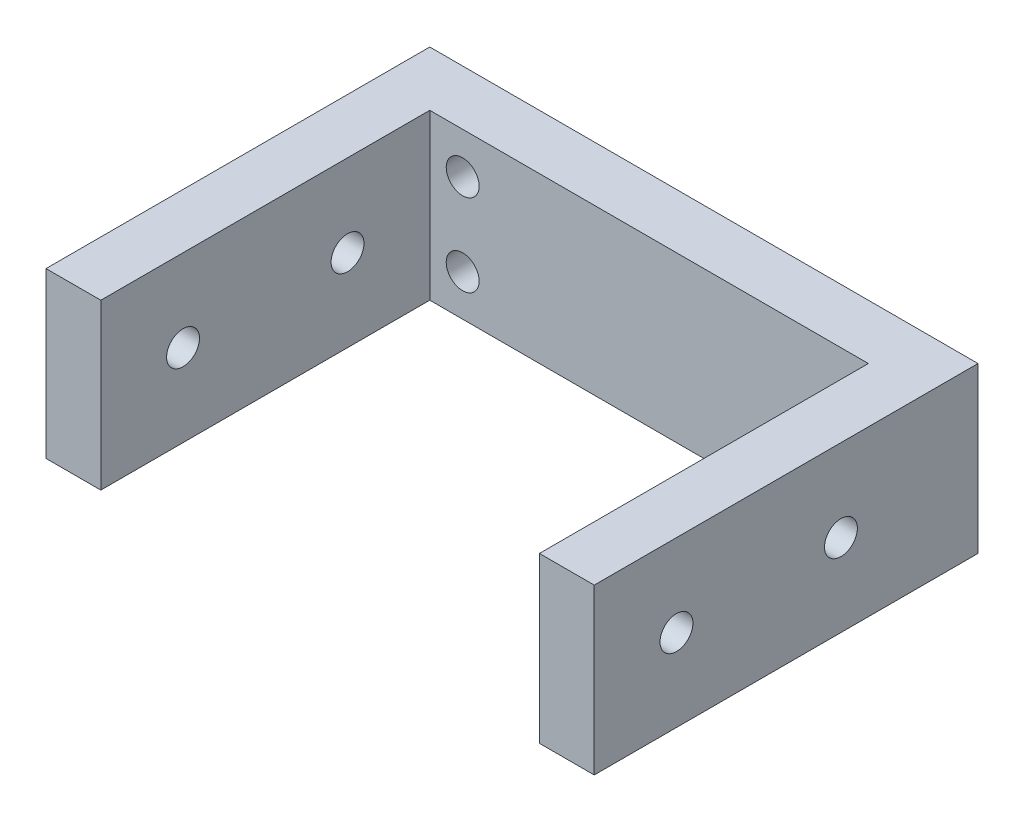
SolidWorks part; units mm, degrees
ref_plane "Front Plane" through (0, 0, 0) normal (0, 0, 1) x (1, 0, 0)
ref_plane "Top Plane" through (0, 0, 0) normal (0, 1, 0) x (1, 0, 0)
ref_plane "Right Plane" through (0, 0, 0) normal (1, 0, 0) x (0, 0, -1)
sketch "Sketch1" plane through (0, 0, 0) normal (0, 0, 1) x (1, 0, 0)
  line L1 (-49.404, 0.1788) -> (0.596, 0.1788)
  line L2 (-49.404, 0.1788) -> (-49.404, -14.8212)
  line L3 (-49.404, -14.8212) -> (0.596, -14.8212)
  line L4 (0.596, 0.1788) -> (0.596, -14.8212)
extrude "Boss-Extrude1" add sketch "Sketch1" along normal blind 2.5 and the other way blind 2.5
sketch "Sketch2" plane through (0, 0, 2.5) normal (0, 0, 1) x (1, 0, 0)
  line L0 (0.596, 0.1788) -> (-49.404, 0.1788) construction
  line L1 (-49.404, -14.8212) -> (-44.404, -14.8212)
  line L2 (-49.404, -14.8212) -> (-49.404, 0.1788)
  line L3 (-49.404, 0.1788) -> (-44.404, 0.1788)
  line L4 (-44.404, -14.8212) -> (-44.404, 0.1788)
extrude "Boss-Extrude2" add sketch "Sketch2" along normal blind 30
sketch "Sketch3" plane through (0, 0, 2.5) normal (0, 0, 1) x (1, 0, 0)
  line L0 (-44.404, -14.8212) -> (0.596, -14.8212) construction
  line L1 (0.596, 0.1788) -> (-4.404, 0.1788)
  line L2 (0.596, 0.1788) -> (0.596, -14.8212)
  line L3 (0.596, -14.8212) -> (-4.404, -14.8212)
  line L4 (-4.404, 0.1788) -> (-4.404, -14.8212)
  dimension "D1" = 5
extrude "Boss-Extrude3" add sketch "Sketch3" along normal blind 30
sketch "Sketch4" plane through (-49.404, 0, 0) normal (-1, 0, 0) x (0, 0, 1)
  circle A0 centre (25, -7.3212) radius 1.5
extrude "Cut-Extrude1" cut sketch "Sketch4" against normal blind 5
sketch "Sketch5" plane through (-49.404, 0, 0) normal (-1, 0, 0) x (0, 0, 1)
  circle A0 centre (10, -7.3212) radius 1.5
extrude "Cut-Extrude2" cut sketch "Sketch5" against normal blind 5
sketch "Sketch6" plane through (0.596, 0, 0) normal (1, 0, 0) x (0, 0, -1)
  circle A0 centre (-25, -7.3212) radius 1.5
extrude "Cut-Extrude3" cut sketch "Sketch6" against normal blind 5
sketch "Sketch7" plane through (0.596, 0, 0) normal (1, 0, 0) x (0, 0, -1)
  circle A0 centre (-10, -7.3212) radius 1.5
extrude "Cut-Extrude5" cut sketch "Sketch7" against normal blind 5
sketch "Sketch11" plane through (0, 0, -2.5) normal (0, 0, -1) x (-1, 0, 0)
  circle A0 centre (41.404, -3.5712) radius 1.5
  circle A1 centre (41.404, -11.0712) radius 1.5
extrude "Cut-Extrude6" cut sketch "Sketch11" against normal blind 5
sketch "Sketch12" plane through (0, 0, -2.5) normal (0, 0, -1) x (-1, 0, 0)
  circle A0 centre (6.404, -7.3212) radius 1.5
extrude "Cut-Extrude7" cut sketch "Sketch12" against normal blind 5
